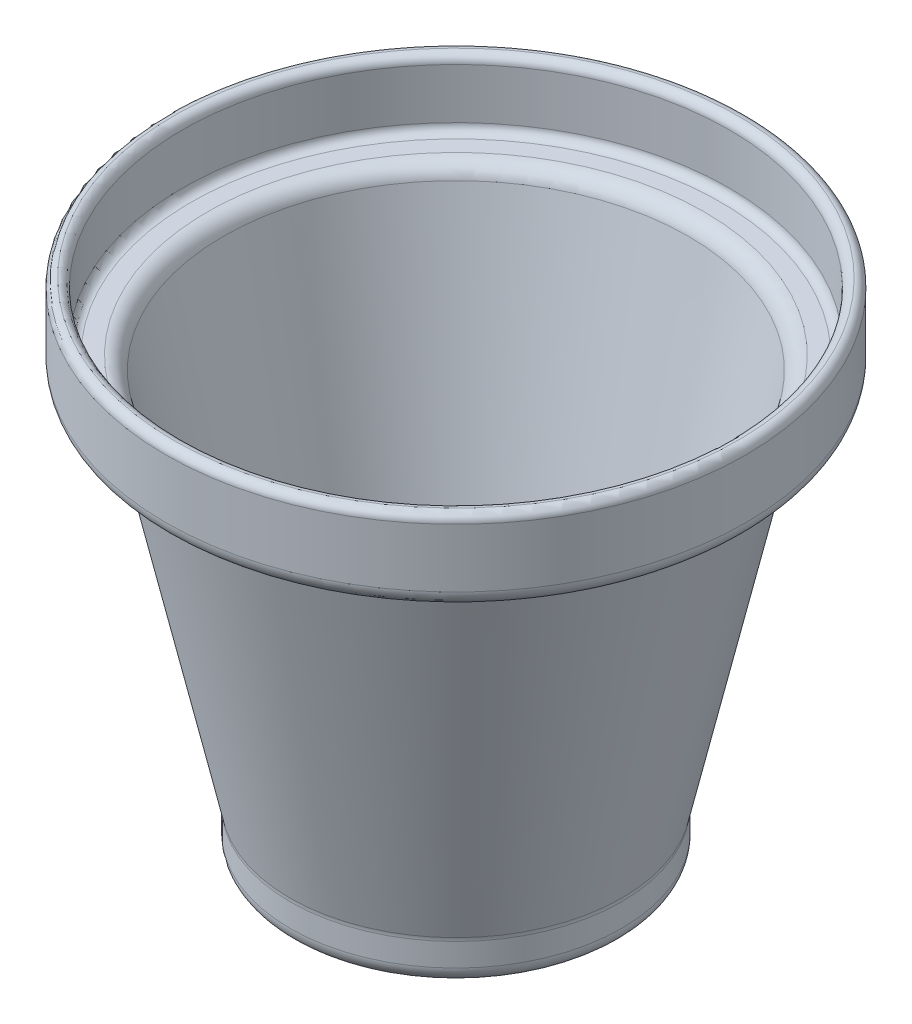
SolidWorks part; units mm, degrees
ref_plane "Front Plane" through (0, 0, 0) normal (0, 0, 1) x (1, 0, 0)
ref_plane "Top Plane" through (0, 0, 0) normal (0, 1, 0) x (1, 0, 0)
ref_plane "Right Plane" through (0, 0, 0) normal (1, 0, 0) x (0, 0, -1)
sketch "Sketch1" plane through (0, 0, 0) normal (0, 0, 1) x (1, 0, 0)
  line L0 (0, 0) -> (25.4, 0)
  line L1 (25.4, 0) -> (25.4, 6.35)
  line L2 (0, 0) -> (0, 76.2) construction
  line L3 (44.45, 76.2) -> (0, 76.2) construction
  line L4 (0, 0) -> (0, 2.54)
  line L5 (25.4, 6.35) -> (38.1, 63.4028)
  line L6 (38.1, 63.4028) -> (44.45, 63.4028)
  line L7 (44.45, 63.4028) -> (44.45, 76.2)
  line L8 (0, 2.54) -> (22.86, 2.54)
  line L9 (22.86, 2.54) -> (22.86, 6.35)
  line L10 (22.86, 6.35) -> (36.0611, 65.9428)
  line L11 (36.0611, 65.9428) -> (41.91, 65.9428)
  line L12 (41.91, 65.9428) -> (41.91, 76.2)
  line L13 (41.91, 76.2) -> (44.45, 76.2)
  line L14 (38.1, 63.4028) -> (38.1, 65.9428) construction
  line L15 (25.4, 6.35) -> (22.86, 6.35) construction
  line L16 (35.6201, 63.9522) -> (38.1, 63.4028) construction
  line L17 (0, 76.2) -> (0, 124.3177) construction
  dimension "D1" = 25.4
  dimension "D2" = 44.45
  dimension "D3" = 12.7972
  dimension "D4" = 6.35
  dimension "D5" = 6.35
  dimension "D6" = 76.2
  dimension "D7" = 2.54
revolve "Revolve1" add sketch "Sketch1" angle 360 about L17
fillet "Fillet1" radius 2.54 5 edges at (0, 65.9428, -36.0611) (0, 63.4028, -44.45) (0, 63.4028, -38.1) (0, 6.35, -25.4) (0, 0, -25.4)
fillet "Fillet2" radius 1.27 5 edges at (0, 6.35, -22.86) (0, 2.54, -22.86) (0, 65.9428, -41.91) (0, 76.2, -44.45) (0, 76.2, -41.91)
ref_axis "Axis1" through (0, 61.4147, 0) along (0, -1, 0)
equation "\"D2@Sketch1\"=1.75*\"D1@Sketch1\""
equation "\"D6@Sketch1\"=3*\"D1@Sketch1\""
